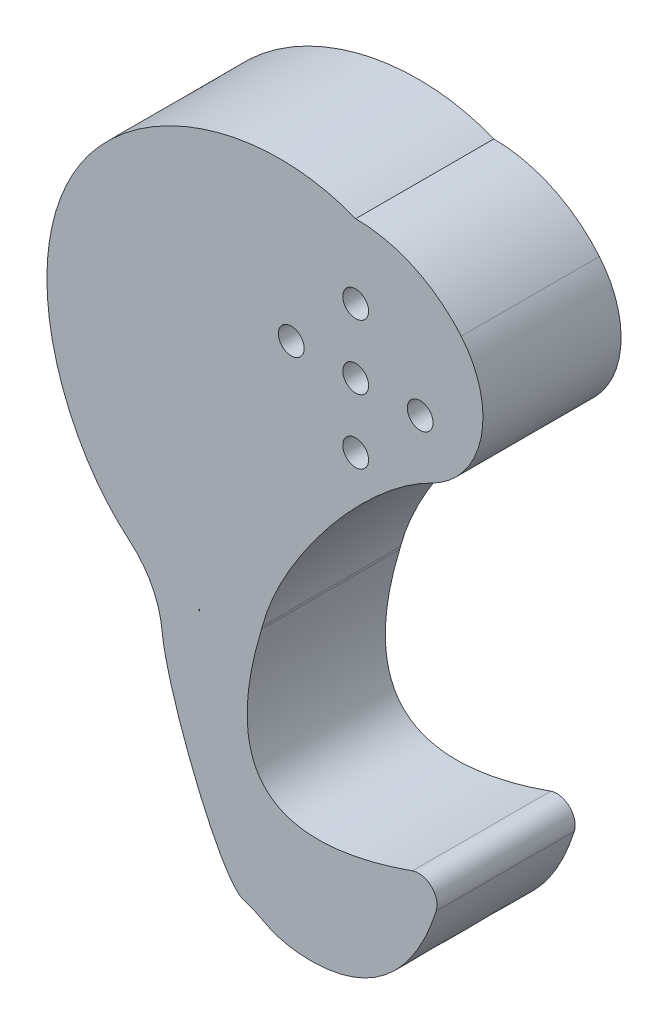
SolidWorks part; units mm, degrees
ref_plane "前视基准面" through (0, 0, 0) normal (0, 0, 1) x (1, 0, 0)
ref_plane "上视基准面" through (0, 0, 0) normal (0, 1, 0) x (1, 0, 0)
ref_plane "右视基准面" through (0, 0, 0) normal (1, 0, 0) x (0, 0, -1)
ref_axis "基准轴1" through (0, 0, -88.99) along (0, 0, 1)
sketch "草图1" plane through (0, 0, 0) normal (0, 0, 1) x (1, 0, 0)
  arc A0 (14.0954, -5.1303) -> (0, 15) centre (0, 0) ccw
  spline S0 degree 3 poles (0, 15) (-0.1746, 15) (-0.4366, 14.9997) (-0.7862, 14.9986) (-1.0489, 14.9975) (-1.3122, 14.996) (-1.5762, 14.9942) (-1.8411, 14.9919) (-2.1069, 14.9891) (-2.3739, 14.9858) (-2.6422, 14.982) (-2.9118, 14.9775) (-3.183, 14.9724) (-3.4559, 14.9664) (-3.7305, 14.9597) (-4.007, 14.952) (-4.2856, 14.9433) (-4.5663, 14.9335) (-4.8494, 14.9224) (-5.1347, 14.9101) (-5.4226, 14.8963) (-5.7131, 14.8809) (-6.0063, 14.8639) (-6.3023, 14.8451) (-6.6012, 14.8243) (-6.903, 14.8015) (-7.208, 14.7764) (-7.516, 14.749) (-7.8273, 14.7191) (-8.1419, 14.6864) (-8.4599, 14.651) (-8.7812, 14.6125) (-9.1061, 14.5709) (-9.4344, 14.5259) (-9.7663, 14.4774) (-10.1018, 14.4251) (-10.441, 14.369) (-10.7838, 14.3088) (-11.1303, 14.2444) (-11.4804, 14.1755) (-11.8343, 14.1019) (-12.1918, 14.0235) (-12.553, 13.94) (-12.9179, 13.8512) (-13.2864, 13.757) (-13.6586, 13.6571) (-14.0343, 13.5513) (-14.4136, 13.4395) (-14.7964, 13.3213) (-15.1826, 13.1966) (-15.5722, 13.0652) (-15.9651, 12.9269) (-16.3612, 12.7814) (-16.7604, 12.6285) (-17.1627, 12.4681) (-17.5679, 12.2999) (-17.9759, 12.1236) (-18.3867, 11.9392) (-18.8, 11.7463) (-19.2158, 11.5448) (-19.634, 11.3344) (-20.0542, 11.115) (-20.4765, 10.8864) (-20.9007, 10.6483) (-21.3265, 10.4003) (-21.7535, 10.1438) (-22.178, 9.8754) (-22.596, 9.5923) (-23.0069, 9.2962) (-23.4102, 8.9872) (-23.8057, 8.6654) (-24.193, 8.3311) (-24.5718, 7.9846) (-24.9417, 7.6261) (-25.3024, 7.256) (-25.6535, 6.8745) (-25.9949, 6.4818) (-26.3262, 6.0784) (-26.647, 5.6645) (-26.9572, 5.2405) (-27.2565, 4.8065) (-27.5445, 4.3631) (-27.8211, 3.9104) (-28.0859, 3.4489) (-28.3389, 2.9789) (-28.5796, 2.5008) (-28.8081, 2.0148) (-29.0239, 1.5214) (-29.227, 1.0209) (-29.4171, 0.5138) (-29.5942, 0.0003) (-29.7579, -0.5192) (-29.9082, -1.0442) (-30.045, -1.5744) (-30.1681, -2.1093) (-30.2773, -2.6487) (-30.3727, -3.1921) (-30.454, -3.7391) (-30.5212, -4.2893) (-30.5742, -4.8423) (-30.613, -5.3977) (-30.6375, -5.9552) (-30.6477, -6.5142) (-30.6435, -7.0745) (-30.6249, -7.6355) (-30.5919, -8.197) (-30.5445, -8.7584) (-30.4828, -9.3194) (-30.4066, -9.8796) (-30.3162, -10.4386) (-30.2115, -10.996) (-30.0925, -11.5513) (-29.9594, -12.1043) (-29.8122, -12.6545) (-29.651, -13.2014) (-29.476, -13.7448) (-29.2871, -14.2842) (-29.0846, -14.8193) (-28.8686, -15.3496) (-28.6391, -15.8749) (-28.3964, -16.3947) (-28.1407, -16.9086) (-27.872, -17.4163) (-27.5906, -17.9175) (-27.2967, -18.4118) (-26.9904, -18.8988) (-26.6719, -19.3783) (-26.3416, -19.8498) (-25.8855, -20.4675) (-25.5263, -20.9179) (-25.2795, -21.212) knots 0 0 0 0 0.008984 0.013482 0.017987 0.022502 0.027029 0.031572 0.036131 0.040709 0.04531 0.049934 0.054586 0.059265 0.063976 0.068721 0.0735 0.078317 0.083174 0.088073 0.093015 0.098004 0.10304 0.108126 0.113264 0.118455 0.123702 0.129006 0.134369 0.139793 0.14528 0.15083 0.156446 0.16213 0.167883 0.173706 0.179601 0.18557 0.191613 0.197734 0.203932 0.210209 0.216567 0.223007 0.229531 0.236139 0.242833 0.249615 0.256485 0.263445 0.270496 0.277639 0.284876 0.292207 0.299634 0.307159 0.314781 0.322503 0.330326 0.33825 0.346277 0.354408 0.362644 0.370986 0.379435 0.387993 0.396619 0.405275 0.41396 0.422674 0.431418 0.440191 0.448994 0.457827 0.46669 0.475583 0.484505 0.493456 0.502437 0.511447 0.520487 0.529555 0.538652 0.547777 0.55693 0.566111 0.57532 0.584555 0.593818 0.603106 0.612421 0.621761 0.631127 0.640517 0.649931 0.659369 0.66883 0.678314 0.68782 0.697347 0.706896 0.716465 0.726054 0.735662 0.745289 0.754934 0.764597 0.774276 0.783972 0.793683 0.803409 0.81315 0.822904 0.83267 0.842449 0.85224 0.862041 0.871853 0.881674 0.891504 0.901341 0.911186 0.921038 0.930895 0.940758 0.950625 0.960495 0.970369 0.980245 1 1 1 1
  spline S1 degree 3 poles (-25.2795, -21.212) (-25.0327, -21.5061) (-24.6501, -21.9369) (-24.1163, -22.4889) (-23.7046, -22.8914) (-23.2819, -23.282) (-22.8486, -23.6605) (-22.4049, -24.0265) (-21.9514, -24.3797) (-21.4885, -24.7199) (-21.0165, -25.0467) (-20.5359, -25.36) (-20.0471, -25.6594) (-19.5507, -25.9449) (-19.047, -26.2162) (-18.5364, -26.4731) (-18.0196, -26.7155) (-17.4968, -26.9432) (-16.9687, -27.156) (-16.4357, -27.354) (-15.8982, -27.537) (-15.3568, -27.7049) (-14.8119, -27.8577) (-14.264, -27.9953) (-13.7136, -28.1177) (-13.1612, -28.225) (-12.6073, -28.3171) (-12.0523, -28.3942) (-11.4967, -28.4561) (-10.941, -28.5031) (-10.3857, -28.5352) (-9.8311, -28.5525) (-9.2779, -28.5552) (-8.7263, -28.5434) (-8.1769, -28.5172) (-7.6301, -28.4768) (-7.0863, -28.4224) (-6.5459, -28.3543) (-6.0093, -28.2726) (-5.4769, -28.1775) (-4.9492, -28.0694) (-4.4264, -27.9484) (-3.909, -27.8149) (-3.3972, -27.6692) (-2.8914, -27.5114) (-2.392, -27.342) (-1.8992, -27.1613) (-1.4133, -26.9695) (-0.9346, -26.7671) (-0.4634, -26.5543) (0, -26.3316) (0.4556, -26.0993) (0.903, -25.8577) (1.342, -25.6072) (1.7725, -25.3482) (2.1942, -25.0811) (2.6072, -24.8063) (3.0111, -24.5241) (3.4059, -24.235) (3.7915, -23.9393) (4.1677, -23.6375) (4.5346, -23.3299) (4.8921, -23.0169) (5.2402, -22.6989) (5.5787, -22.3763) (5.9078, -22.0495) (6.2274, -21.7189) (6.5376, -21.3849) (6.8384, -21.0477) (7.1298, -20.7079) (7.412, -20.3657) (7.685, -20.0215) (7.9489, -19.6757) (8.2039, -19.3286) (8.45, -18.9805) (8.6875, -18.6318) (8.9164, -18.2828) (9.1369, -17.9338) (9.3493, -17.585) (9.5536, -17.2367) (9.7501, -16.8893) (9.9391, -16.543) (10.1206, -16.1981) (10.2951, -15.8546) (10.4626, -15.513) (10.6234, -15.1734) (10.7778, -14.836) (10.926, -14.5009) (11.0683, -14.1684) (11.2049, -13.8386) (11.3362, -13.5116) (11.4624, -13.1876) (11.5837, -12.8667) (11.7005, -12.5489) (11.8131, -12.2344) (11.9216, -11.9232) (12.0264, -11.6154) (12.1278, -11.3109) (12.226, -11.0099) (12.3214, -10.7123) (12.4141, -10.4182) (12.5046, -10.1274) (12.5929, -9.8401) (12.6795, -9.556) (12.7645, -9.2752) (12.8482, -8.9976) (12.9308, -8.7232) (13.0127, -8.4517) (13.0939, -8.1831) (13.1748, -7.9172) (13.2556, -7.654) (13.3364, -7.3933) (13.4175, -7.135) (13.499, -6.8788) (13.5811, -6.6245) (13.664, -6.3721) (13.7479, -6.1213) (13.8328, -5.872) (13.9475, -5.5413) (14.0357, -5.2944) (14.0954, -5.1303) knots 0 0 0 0 0.02127 0.031904 0.042535 0.053163 0.063787 0.074406 0.08502 0.095628 0.106228 0.116821 0.127405 0.13798 0.148544 0.159097 0.169638 0.180166 0.19068 0.20118 0.211663 0.22213 0.23258 0.243011 0.253422 0.263812 0.274181 0.284528 0.29485 0.305148 0.31542 0.325664 0.335881 0.346068 0.356224 0.366349 0.376441 0.386499 0.396521 0.406507 0.416454 0.426363 0.436231 0.446057 0.45584 0.465578 0.475271 0.484916 0.494513 0.50406 0.513556 0.522999 0.532388 0.541722 0.550999 0.560217 0.569377 0.578475 0.587511 0.596484 0.605392 0.614233 0.623007 0.631713 0.640348 0.648912 0.657404 0.665822 0.674165 0.682432 0.690623 0.698735 0.706768 0.714721 0.722594 0.730384 0.738092 0.745717 0.753257 0.760713 0.768084 0.775369 0.782568 0.78968 0.796706 0.803645 0.810497 0.817263 0.823941 0.830534 0.83704 0.843461 0.849797 0.856048 0.862216 0.868302 0.874307 0.880232 0.886079 0.891849 0.897544 0.903166 0.908717 0.9142 0.919616 0.92497 0.930262 0.935498 0.940679 0.945809 0.950892 0.955931 0.96093 0.965894 0.970826 0.97573 0.980612 0.985475 0.990325 1 1 1 1
extrude "凸台-拉伸1" add sketch "草图1" along normal blind 15
sketch "草图2" plane through (0, 0, 0) normal (0, 0, 1) x (1, 0, 0)
  line L0 (0.9848, -0.1736) -> (0.6375, -2.1433)
  line L1 (0.6375, -2.1433) -> (-1.3321, -1.796)
  line L2 (-1.3321, -1.796) -> (-0.9848, 0.1736)
  arc A0 (0.9848, -0.1736) -> (-0.9848, 0.1736) centre (0, 0) ccw
extrude "切除-拉伸1" [suppressed] cut sketch "草图2" against normal blind 10 and the other way blind 10
sketch "草图3" plane through (0, 0, 15) normal (0, 0, 1) x (1, 0, 0)
  line L0 (7, 0) -> (0, 0) construction
  circle A0 centre (0, 0) radius 1.4
  circle A1 centre (7, 0) radius 1.4
  circle A2 centre (0, -7) radius 1.4
  circle A3 centre (-7, 0) radius 1.4
  circle A4 centre (0, 7) radius 1.4
  point P13 (0, 0)
  dimension "D1" = 2.8
  dimension "D2" = 2.8
  dimension "D3" = 7
  dimension "D4" = 4
extrude "切除-拉伸2" cut sketch "草图3" against normal through all
sketch "草图4" plane through (0, 0, 0) normal (0, 0, -1) x (-1, 0, 0)
  spline S0 degree 3 poles (-14.5415, -65.5031) (-26.7252, 15.3889) (8.4425, -18.7625) (12.7559, -38.1787) (-14.5415, -65.5031) (-26.7252, 15.3889) (8.4425, -18.7625) knots -0.730317 -0.605024 -0.425968 0 0.269683 0.394976 0.574032 1 1.269683 1.394976 1.574032 only from (-14.0954, -5.1303) to (-14.0954, -5.1303)
extrude "切除-拉伸3" cut sketch "草图4" against normal through all
sketch "草图5" plane through (0, 0, 0) normal (0, 0, -1) x (-1, 0, 0)
  circle A1 centre (0, 0) radius 1.4 construction
  spline S0 degree 2 poles (10.1719, -28.5412) (17.6838, -53.1512) (-9.708, -41.8898) knots 0 0 0 1 1 1
  spline S1 degree 3 poles (-9.708, -41.8898) (-2.463, -79.7631) (48.0134, -36.7446) (17.334, -27.0078) knots 0 0 0 0 1 1 1 1
  spline S2 degree 3 poles (-1755.3317, -907.4465) (-73.037, 227.2275) (64.2984, 19.0722) (23.983, -22.6268) (23.2875, -23.2879) (22.4102, -24.0326) (21.4934, -24.7262) (20.5406, -25.3665) (19.555, -25.9516) (18.5405, -26.4799) (17.5006, -26.9501) (16.4391, -27.3611) (15.3599, -27.712) (14.2668, -28.0025) (13.1637, -28.2323) (12.0545, -28.4014) (11.1271, -28.4924) (-48.0608, -31.9137) (-117.9167, 212.8962) (1876.8784, 657.3507) knots -3.159689 -3.159689 -3.159689 -3.159689 0.02127 0.031904 0.053163 0.074406 0.095628 0.116821 0.13798 0.159097 0.180166 0.20118 0.22213 0.243011 0.263812 0.284528 0.305148 0.31542 3.568634 3.568634 3.568634 3.568634 only from (25.2795, -21.212) to (10.1719, -28.5412) construction
  spline S3 degree 3 poles (17.334, -27.0078) (16.8618, -27.2011) (16.0276, -27.5069) (14.8148, -27.8648) (13.7163, -28.125) (12.6097, -28.3244) (11.4988, -28.4634) (10.685, -28.5213) (10.243, -28.5388) (10.1719, -28.5412) knots 0.183396 0.183396 0.183396 0.183396 0.211663 0.23258 0.253422 0.274181 0.29485 0.31542 0.31936 0.31936 0.31936 0.31936
  point P4 (11.6073, -53.7612)
  dimension "D1" = 57
  dimension "D2" = 43
extrude "凸台-拉伸2" add sketch "草图5" against normal up to surface (15 mm away) up to face at (8.4, 0, 15)
fillet "圆角1" radius 2 1 edges at (9.708, -41.8898, 7.5)
fillet "圆角2" radius 10 1 edges at (-10.1719, -28.5412, 7.5)
fillet "圆角3" radius 10 1 edges at (14.0954, -5.1303, 7.5)
sketch "草图6" plane through (0, 0, 0) normal (0, 0, -1) x (-1, 0, 0)
  arc A1 (17.334, -28.8385) -> (17.334, -27.0078) centre (6.2989, -27.9232) ccw
  spline S0 degree 2 poles (17.334, -28.8385) (28.0523, -41.2239) (13.7306, -54.9524) knots 0 0 0 1 1 1
  spline S1 degree 3 poles (492.4484, 819.5946) (-736.513, -882.5278) (916.4004, 626.6626) (-881.4057, -465.4402) knots -1.33911 -1.33911 -1.33911 -1.33911 2.367146 2.367146 2.367146 2.367146 only from (-8.741, -45.741) to (17.334, -27.0078) construction
  spline S2 degree 3 poles (13.7306, -54.9524) (25.9418, -48.9195) (34.8204, -32.5575) (17.334, -27.0078) knots 0.430027 0.430027 0.430027 0.430027 1 1 1 1
extrude "切除-拉伸4" cut sketch "草图6" against normal blind 20
fillet "圆角4" [suppressed] radius 10
sketch "草图7" plane through (0, 0, 0) normal (0, 0, -1) x (-1, 0, 0)
  parabola Q0 (17.334, -28.8385) -> (13.7306, -54.9524) focus (15.2331, -39.3289) apex (21.9027, -38.9711) construction
  spline S0 degree 3 poles (45.5205, -46.0023) (13.4431, -20.4974) (18.8941, -39.0495) (16.6277, -45.9682) (10.6169, -60.7262) (45.5205, -46.0023) (13.4431, -20.4974) (18.8941, -39.0495) knots -0.722896 -0.612877 -0.318455 0 0.142925 0.277104 0.387123 0.681545 1 1.142925 1.277104 1.387123 only from (17.334, -28.8385) to (17.334, -28.8385)
extrude "切除-拉伸5" cut sketch "草图7" against normal blind 20
sketch "草图8" plane through (0, 0, 0) normal (0, 0, -1) x (-1, 0, 0)
  line L2 (16.9763, -30.5816) -> (17.0247, -29.8177)
  arc A0 (17.334, -28.8385) -> (17.334, -27.0078) centre (6.2989, -27.9232) ccw construction
  arc A1 (17.334, -28.8385) -> (17.334, -27.0078) centre (6.2989, -27.9232) ccw
  spline S0 degree 3 poles (0, 15) (9.9555, 18.9944) (30.4708, 12.3487) (35.8972, -12.3609) (27.2904, -26.9922) (20.6189, -30.0876) knots 0 0 0 0 0.427134 0.68274 0.947421 0.947421 0.947421 0.947421
  spline S1 degree 3 poles (45.5205, -46.0023) (13.4431, -20.4974) (18.8941, -39.0495) (16.6277, -45.9682) (10.6169, -60.7262) (45.5205, -46.0023) (13.4431, -20.4974) (18.8941, -39.0495) knots -0.722896 -0.612877 -0.318455 0 0.142925 0.277104 0.387123 0.681545 1 1.142925 1.277104 1.387123 only from (17.334, -28.8385) to (17.334, -28.8385) construction
  spline S2 degree 3 poles (-195.1738, 995.7662) (-169.6477, -35.158) (-84.4144, 15.2544) (0.9619, 14.9981) (1.5785, 14.9947) (2.3773, 14.9865) (3.2804, 14.9717) (4.2006, 14.948) (5.1416, 14.9115) (6.0142, 14.8656) (6.9118, 14.8034) (7.7296, 14.7308) (8.4637, 14.6518) (9.1101, 14.5718) (9.7706, 14.4783) (10.4455, 14.37) (11.135, 14.2454) (11.8392, 14.1029) (12.5582, 13.9409) (13.2918, 13.758) (14.0399, 13.5523) (14.8022, 13.3222) (15.7135, 13.0214) (16.7772, 12.6305) (17.9935, 12.1253) (18.9459, 11.6806) (19.634, 11.3344) (20.0542, 11.115) (20.4765, 10.8864) (20.9007, 10.6483) (21.3265, 10.4003) (21.7535, 10.1438) (22.178, 9.8754) (22.596, 9.5923) (23.0069, 9.2962) (23.4102, 8.9872) (23.9385, 8.5574) (24.5781, 7.9888) (25.3089, 7.2598) (26.0016, 6.4853) (26.6539, 5.6676) (27.2635, 4.8092) (27.8282, 3.9127) (28.3461, 2.9808) (28.8153, 2.0164) (29.2343, 1.0221) (29.6015, 0.0011) (29.9156, -1.0437) (30.1754, -2.1092) (30.38, -3.1922) (30.5285, -4.2898) (30.6203, -5.3985) (30.6549, -6.5153) (30.632, -7.6369) (30.5516, -8.7601) (30.4136, -9.8816) (30.2183, -10.9982) (29.9662, -12.1068) (29.6577, -13.2042) (29.2936, -14.2872) (28.875, -15.3529) (28.4027, -16.3981) (27.8781, -17.4201) (27.3026, -18.4158) (26.782, -19.2212) (26.3416, -19.8498) (-3.5055, -60.2739) (-162.5187, -2.5838) (199.2859, 963.5285) knots -4.365889 -4.365889 -4.365889 -4.365889 0.008984 0.013482 0.027029 0.040709 0.054586 0.0735 0.088073 0.10304 0.118455 0.134369 0.14528 0.156446 0.167883 0.179601 0.191613 0.203932 0.216567 0.229531 0.242833 0.256485 0.270496 0.292207 0.314781 0.33825 0.346277 0.354408 0.362644 0.370986 0.379435 0.387993 0.396619 0.405275 0.41396 0.422674 0.431418 0.448994 0.46669 0.484505 0.502437 0.520487 0.538652 0.55693 0.57532 0.593818 0.612421 0.631127 0.649931 0.66883 0.68782 0.706896 0.726054 0.745289 0.764597 0.783972 0.803409 0.822904 0.842449 0.862041 0.881674 0.901341 0.921038 0.940758 0.960495 0.970369 0.980245 3.545706 3.545706 3.545706 3.545706 only from (0, 15) to (25.2795, -21.212) construction
  spline S3 degree 3 poles (0, 15) (0.262, 15) (0.6993, 14.9992) (1.4015, 14.9958) (2.11, 14.9897) (2.916, 14.9783) (3.83, 14.9587) (4.7638, 14.9282) (5.7207, 14.8825) (6.6097, 14.8262) (7.4192, 14.7598) (8.1457, 14.6873) (8.7852, 14.6134) (9.4386, 14.5268) (10.1063, 14.4261) (10.7884, 14.3098) (11.4852, 14.1764) (12.1968, 14.0244) (12.9232, 13.8522) (13.6641, 13.658) (14.4193, 13.4404) (15.3226, 13.1551) (16.3777, 12.7835) (17.444, 12.358) (18.3934, 11.9397) (19.08, 11.6131) (19.634, 11.3344) (20.0542, 11.115) (20.4765, 10.8864) (20.9007, 10.6483) (21.3265, 10.4003) (21.7535, 10.1438) (22.178, 9.8754) (22.596, 9.5923) (23.0069, 9.2962) (23.4102, 8.9872) (23.9385, 8.5574) (24.5781, 7.9888) (25.3089, 7.2598) (26.0016, 6.4853) (26.6539, 5.6676) (27.2635, 4.8092) (27.8282, 3.9127) (28.3461, 2.9808) (28.8153, 2.0164) (29.2343, 1.0221) (29.6015, 0.0011) (29.9156, -1.0437) (30.1754, -2.1092) (30.38, -3.1922) (30.5285, -4.2898) (30.6203, -5.3985) (30.6549, -6.5153) (30.632, -7.6369) (30.5516, -8.7601) (30.4136, -9.8816) (30.2183, -10.9982) (29.9662, -12.1068) (29.6577, -13.2042) (29.2936, -14.2872) (28.875, -15.3529) (28.4027, -16.3981) (27.8781, -17.4201) (27.3026, -18.4158) (26.6777, -19.3824) (26.0052, -20.3174) (25.5263, -20.9179) (25.2795, -21.212) knots 0 0 0 0 0.013482 0.022502 0.036131 0.049934 0.063976 0.083174 0.098004 0.113264 0.129006 0.139793 0.15083 0.16213 0.173706 0.18557 0.197734 0.210209 0.223007 0.236139 0.249615 0.263445 0.284876 0.307159 0.322503 0.33825 0.346277 0.354408 0.362644 0.370986 0.379435 0.387993 0.396619 0.405275 0.41396 0.422674 0.431418 0.448994 0.46669 0.484505 0.502437 0.520487 0.538652 0.55693 0.57532 0.593818 0.612421 0.631127 0.649931 0.66883 0.68782 0.706896 0.726054 0.745289 0.764597 0.783972 0.803409 0.822904 0.842449 0.862041 0.881674 0.901341 0.921038 0.940758 0.960495 0.980245 1 1 1 1
  spline S4 degree 3 poles (-911.73, -370.5125) (-24.8055, 149.9602) (56.2113, 10.7076) (23.983, -22.6268) (23.2875, -23.2879) (22.4102, -24.0326) (21.4934, -24.7262) (20.5406, -25.3665) (19.555, -25.9516) (18.7091, -26.3921) (18.0196, -26.7155) (-24.7807, -45.358) (-128.1742, 81.0325) (695.2443, 708.1219) knots -2.515208 -2.515208 -2.515208 -2.515208 0.02127 0.031904 0.053163 0.074406 0.095628 0.116821 0.13798 0.159097 0.169638 0.180166 2.745072 2.745072 2.745072 2.745072 only from (25.2795, -21.212) to (17.334, -27.0078) construction
  spline S5 degree 3 poles (17.334, -28.8385) (17.1756, -29.0948) (17.0773, -29.4266) (17.0247, -29.8177) knots 0 0 0 0 0.023193 0.023193 0.023193 0.023193
  spline S6 degree 3 poles (25.2795, -21.212) (25.0327, -21.5061) (24.5226, -22.0804) (23.7103, -22.8971) (22.854, -23.6665) (21.9566, -24.3859) (21.0213, -25.0531) (20.0517, -25.6661) (19.0512, -26.223) (18.1418, -26.6649) (17.5638, -26.9137) (17.334, -27.0078) knots 0 0 0 0 0.02127 0.042535 0.063787 0.08502 0.106228 0.127405 0.148544 0.169638 0.183396 0.183396 0.183396 0.183396
  spline S7 degree 3 poles (20.6189, -30.0876) (22.0845, -35.2066) (15.9386, -51.7756) (16.9763, -30.5816) knots 0 0 0 0 1 1 1 1
extrude "凸台-拉伸3" add sketch "草图8" against normal up to surface (15 mm away) up to face at (8.4, 0, 15)
fillet "圆角6" [suppressed] radius 2
fillet "圆角7" [suppressed] radius 10
fillet "圆角8" [suppressed] radius 10
fillet "圆角10" radius 10 2 edges at (-14.4538, -54.244, 7.5) (-17.7987, -41.0199, 7.5)
fillet "圆角11" radius 5 1 edges at (-20.6189, -30.0876, 7.5)
fillet "圆角12" radius 10 1 edges
sketch "草图9" plane through (0, 0, 0) normal (0, 0, -1) x (-1, 0, 0)
  arc A0 (6.3576, -57.1486) -> (14.9372, -50.2722) centre (5.4233, -47.1923) ccw construction
  spline S0 degree 3 poles (10.8685, -42.8683) (23.1231, -26.6898) (19.0215, -44.0853) (10.8151, -60.8898) (10.8685, -42.8683) (23.1231, -26.6898) (19.0215, -44.0853) knots -0.80555 -0.505595 -0.321007 0 0.19445 0.494405 0.678993 1 1.19445 1.494405 1.678993 only from (20.8334, -32.6499) to (20.8334, -32.6499)
extrude "凸台-拉伸4" add sketch "草图9" against normal up to surface (15 mm away) up to face at (-6.2673, -28.8454, 15)
fillet "圆角13" radius 10 2 edges at (-20.8334, -32.6499, 7.5) (-11.6773, -54.9954, 7.5)
